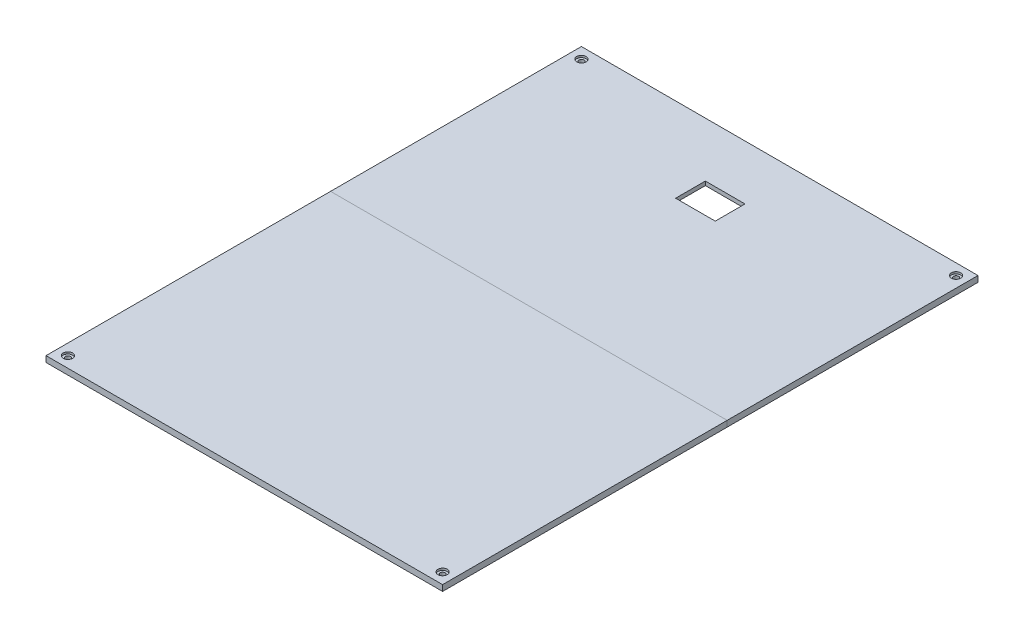
SolidWorks part; units mm, degrees
material "PLA"
ref_plane "Спереди" through (0, 0, 0) normal (0, 0, 1) x (1, 0, 0)
ref_plane "Сверху" through (0, 0, 0) normal (0, 1, 0) x (1, 0, 0)
ref_plane "Справа" through (0, 0, 0) normal (1, 0, 0) x (0, 0, -1)
sketch "Эскиз1" plane through (0, 0, 0) normal (0, 1, 0) x (1, 0, 0)
  line L1 (100, 135) -> (-100, 135)
  line L2 (100, 135) -> (100, -135)
  line L3 (100, -135) -> (-100, -135)
  line L4 (-100, 135) -> (-100, -135)
  line L5 (100, 135) -> (-100, -135) construction
  line L6 (100, -135) -> (-100, 135) construction
  point P0 (0, 0)
  dimension "D1" = 200
  dimension "D2" = 270
extrude "Бобышка-Вытянуть1" add sketch "Эскиз1" along normal blind 3
sketch "Эскиз2" plane through (0, 3, 0) normal (0, 1, 0) x (1, 0, 0)
  line L0 (0, 0) -> (0, 50000) construction
  line L1 (0, 0) -> (-50000, 0) construction
  line L2 (-100, 135) -> (-100, -135) construction
  line L3 (100, 135) -> (-100, 135) construction
  line L4 (100, 133) -> (-98, 133) construction
  line L5 (-98, 133) -> (-98, -135) construction
  line L6 (-100, 135) -> (-100, -135) construction
  line L7 (100, 135) -> (-100, 135) construction
  line L8 (-86, 133) -> (-98, 121) construction
  line L9 (-98, 133) -> (-92, 127) construction
  circle A0 centre (-94.4749, 129.4749) radius 1.3
  circle A1 centre (94.4749, 129.4749) radius 1.3
  circle A2 centre (94.4749, -129.4749) radius 1.3
  circle A3 centre (-94.4749, -129.4749) radius 1.3
  circle A4 centre (-94.4749, 129.4749) radius 2 construction
  point P23 (-94.4749, 129.4749)
  point P24 (-94.5048, 129.445)
  point P25 (0, 0)
  point P26 (-93.1211, 125.8789)
  point P27 (-92, 127)
  dimension "D1" = 2.6
  dimension "D7" = 4
  dimension "D2" = 1.5
  dimension "D5" = 12
  dimension "D6" = 45
  dimension "D4" = 2
extrude "Вырез-Вытянуть1" cut sketch "Эскиз2" against normal through all
sketch "Эскиз3" plane through (0, 3, 0) normal (0, 1, 0) x (1, 0, 0)
  circle A0 centre (-94.4749, 129.4749) radius 2.375
  circle A1 centre (94.4749, 129.4749) radius 2.375
  circle A2 centre (-94.4749, -129.4749) radius 2.375
  circle A3 centre (94.4749, -129.4749) radius 2.375
  dimension "D1" = 4.75
extrude "Вырез-Вытянуть2" cut sketch "Эскиз3" against normal blind 1
sketch "Эскиз4" plane through (0, 3, 0) normal (0, 1, 0) x (1, 0, 0)
  line L0 (0, 0) -> (0, 50000) construction
  line L1 (10, 107.5) -> (-10, 107.5)
  line L2 (10, 107.5) -> (10, 92.5)
  line L3 (10, 92.5) -> (-10, 92.5)
  line L4 (-10, 107.5) -> (-10, 92.5)
  line L5 (10, 107.5) -> (-10, 92.5) construction
  line L6 (10, 92.5) -> (-10, 107.5) construction
  line L7 (100, 135) -> (-100, 135) construction
  point P0 (0, 100)
  dimension "D1" = 20
  dimension "D2" = 15
  dimension "D3" = 35
extrude "Вырез-Вытянуть3" cut sketch "Эскиз4" against normal through all
sketch "Эскиз5" plane through (0, 0, 0) normal (0, -1, 0) x (1, 0, 0)
  line L0 (100, -135) -> (-100, -135) construction
  line L1 (100, 135) -> (100, -135) construction
  circle A0 centre (-3.9, -120.15) radius 1.75
  circle A1 centre (6.25, -88.45) radius 1.75
  circle A2 centre (-3.9, -120.15) radius 2.75
  circle A3 centre (6.25, -88.45) radius 2.75
  dimension "D1" = 3.5
  dimension "D2" = 14.85
  dimension "D3" = 103.9
  dimension "D4" = 10.15
  dimension "D5" = 31.7
  dimension "D6" = 1
extrude "Бобышка-Вытянуть2" add sketch "Эскиз5" along normal blind 2.8
ref_plane "Плоскость1" through (0, 0, -8.5) normal (0, 0, 1) x (1, 0, 0)
split "Разделить1" trim tools "Плоскость1" bodies to split 107 resulting bodies 108 109
chamfer "Фаска1" distance 1 angle 45 4 edges at (0, 0, -107.5) (-10, 0, -100) (0, 0, -92.5) (10, 0, -100)
